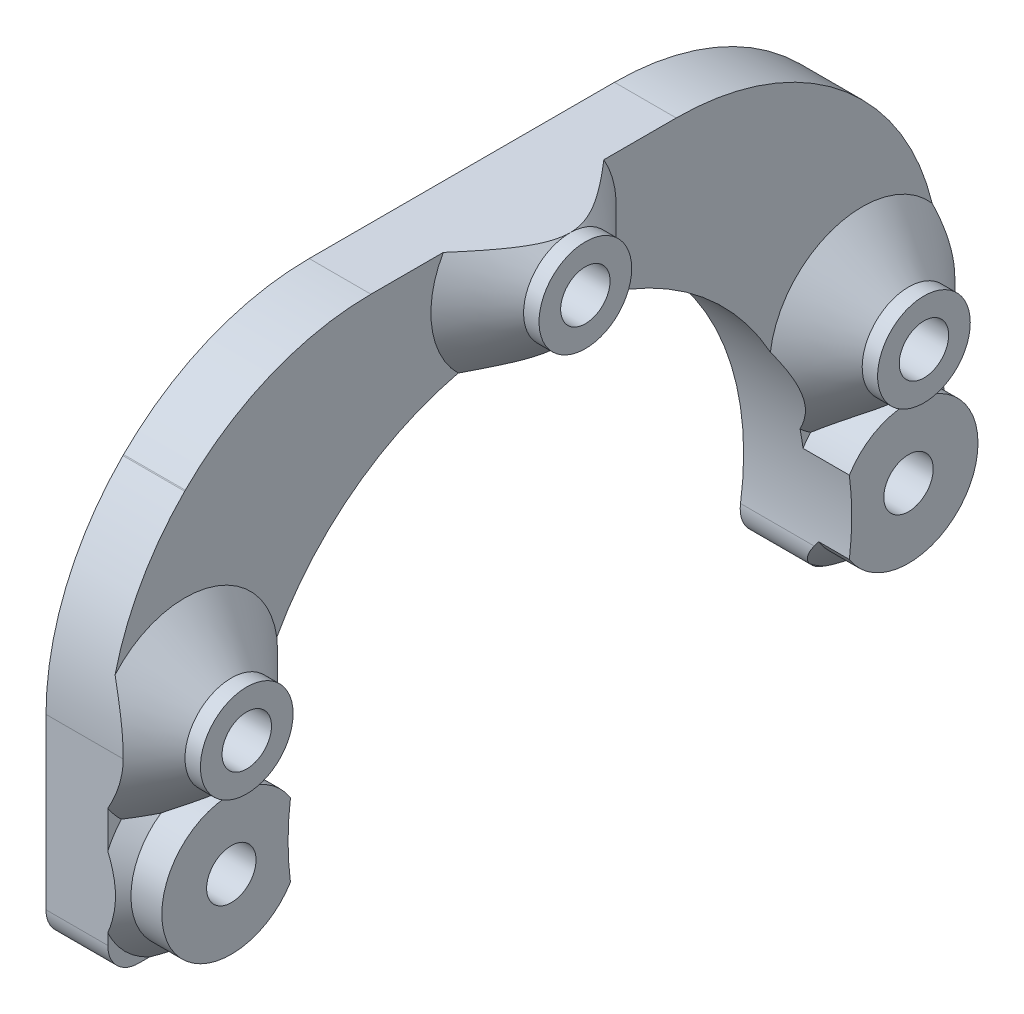
SolidWorks part; units mm, degrees
ref_plane "前视基准面" through (0, 0, 0) normal (0, 0, 1) x (1, 0, 0)
ref_plane "上视基准面" through (0, 0, 0) normal (0, 1, 0) x (1, 0, 0)
ref_plane "右视基准面" through (0, 0, 0) normal (1, 0, 0) x (0, 0, -1)
other "Configuration Table"
sketch "草图1" plane through (0, 0, 0) normal (1, 0, 0) x (0, 0, -1)
  line L1 (0, 0) -> (53.85, 0)
  line L2 (0, 0) -> (0, -30)
  line L3 (0, -30) -> (53.85, -30)
  line L4 (53.85, 0) -> (53.85, -30)
  circle A0 centre (5, -25) radius 1.6
  circle A1 centre (48.85, -25) radius 1.6
  dimension "D3" = 3.2
  dimension "D4" = 3.2
  dimension "D1" = 43.85
  dimension "D2" = 53.85
  dimension "D5" = 5
  dimension "D6" = 5
  dimension "D7" = 5
  dimension "D8" = 30
extrude "凸台-拉伸1" add sketch "草图1" along normal blind 4
sketch "草图7" plane through (4, 0, 0) normal (1, 0, 0) x (0, 0, -1)
  circle A0 centre (5, -25) radius 1.6
  circle A1 centre (48.85, -25) radius 1.6
  circle A2 centre (5, -25) radius 4.5
  circle A3 centre (48.85, -25) radius 4.5
  dimension "D1" = 9
  dimension "D2" = 9
extrude "凸台-拉伸3" add sketch "草图7" along normal blind 3
sketch "草图2" plane through (4, 0, 0) normal (1, 0, 0) x (0, 0, -1)
  line L0 (0, -30) -> (53.85, -30) construction
  circle A0 centre (26.925, -25) radius 18.25
  point P4 (26.925, -30)
  dimension "D3" = 36.5
  dimension "D1" = 5
  dimension "D2" = 0
extrude "切除-拉伸1" cut sketch "草图2" against normal blind 4 and the other way through all
chamfer "倒角1" distance 10 angle 45 2 edges at (2, 0, -53.85) (2, 0, 0)
sketch "草图3" plane through (4, 0, 0) normal (1, 0, 0) x (0, 0, -1)
  line L0 (53.85, -30) -> (53.85, -10) construction
  line L1 (0, -10) -> (0, -30) construction
  line L3 (0, -30) -> (9.3733, -30) construction
  line L4 (44.4767, -30) -> (53.85, -30) construction
  line L5 (43.85, 0) -> (10, 0) construction
  circle A0 centre (5, -17) radius 3
  circle A1 centre (48.85, -17) radius 3
  circle A2 centre (26.925, -3) radius 3
  point P16 (26.925, 0)
  dimension "D1" = 6
  dimension "D2" = 6
  dimension "D5" = 13
  dimension "D6" = 13
  dimension "D7" = 0
  dimension "D8" = 3
  dimension "D9" = 6
  dimension "D3" = 5
  dimension "D4" = 5
extrude "凸台-拉伸2" add sketch "草图3" along normal blind 4
sketch "草图4" plane through (8, 0, 0) normal (1, 0, 0) x (0, 0, -1)
  circle A0 centre (5, -17) radius 1.6
  circle A1 centre (48.85, -17) radius 1.6
  circle A2 centre (26.925, -3) radius 1.6
  dimension "D1" = 3.2
  dimension "D2" = 3.2
  dimension "D3" = 3.2
extrude "切除-拉伸2" cut sketch "草图4" against normal through all
chamfer "倒角3" distance 3 angle 45 3 edges at (4, -17, -51.85) (4, -17, -8) (4, -3, -29.925)
chamfer "倒角4" distance 1 angle 45 2 edges at (4, -28.5992, -51.5511) (4, -28.5992, -2.2989)
fillet "圆角1" radius 2 4 edges at (2, -30, -44.4767) (2, -30, -9.3733) (2, -30, -53.85) (2, -30, 0)
fillet "圆角2" radius 17 4 edges at (2, -10, -53.85) (2, 0, -43.85) (2, -10, 0) (2, 0, -10)
equation "\"D2@草图1\"=\"D1@草图1\"+10"
